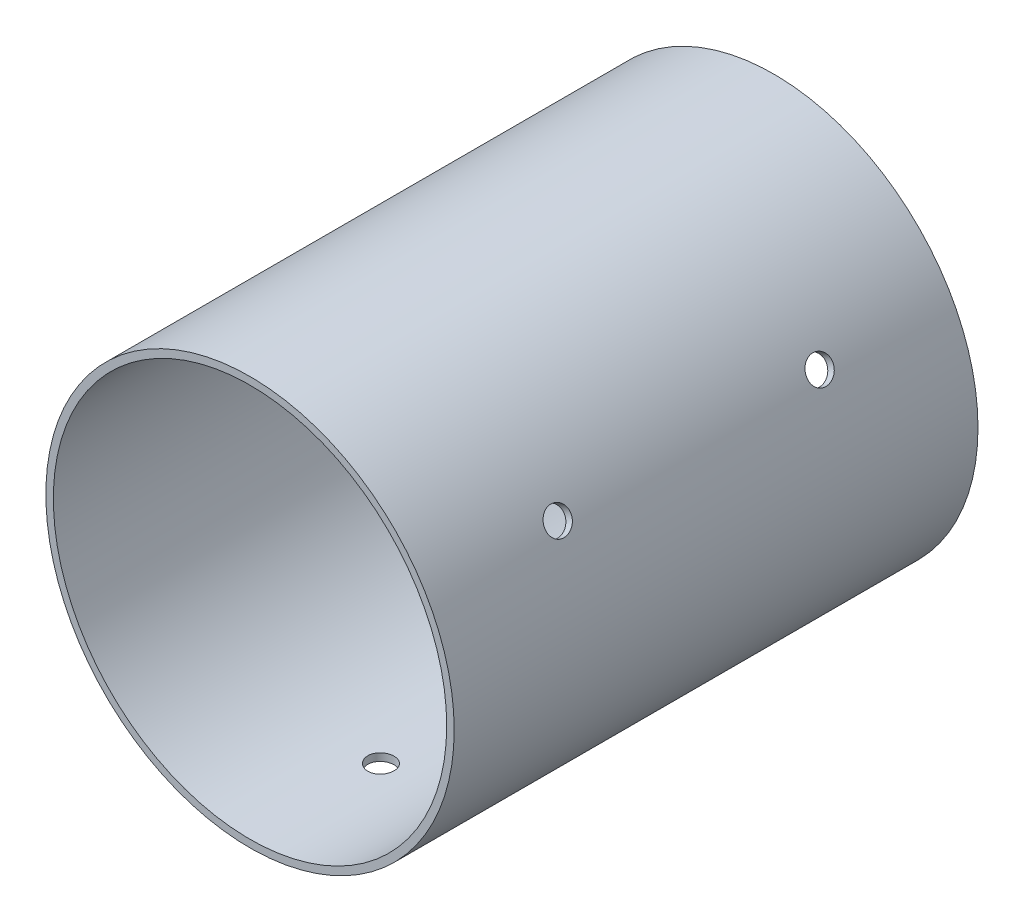
SolidWorks part; units mm, degrees
ref_plane "Front Plane" through (0, 0, 0) normal (0, 0, 1) x (1, 0, 0)
ref_plane "Top Plane" through (0, 0, 0) normal (0, 1, 0) x (1, 0, 0)
ref_plane "Right Plane" through (0, 0, 0) normal (1, 0, 0) x (0, 0, -1)
sketch "Sketch1" plane through (0, 0, 0) normal (0, 0, 1) x (1, 0, 0)
  circle A0 centre (0, 0) radius 49.5046
  circle A1 centre (0, 0) radius 47.6885
  dimension "D1" = 99.0092
  dimension "D2" = 95.377
extrude "Boss-Extrude1" add sketch "Sketch1" along normal blind 127
ref_axis "Axis1" through (0, 0, 127) along (0, 0, -1)
ref_plane "Plane1" through (0, 0, 0) normal (0.866, 0.5, 0) x (0, 0, -1)
sketch "Sketch4" plane through (0, 0, 0) normal (0, 1, 0) x (1, 0, 0)
  line L0 (0, -127) -> (0, 0) construction
  line L1 (-49.5046, -127) -> (49.5046, -127) construction
  line L2 (47.6885, 0) -> (-47.6885, 0) construction
  circle A0 centre (0, -31.75) radius 3.175
  circle A1 centre (0, -95.25) radius 3.175
  dimension "D1" = 6.35
  dimension "D2" = 31.75
  dimension "1.25" = 31.75
extrude "Cut-Extrude3" cut sketch "Sketch4" against normal through all
pattern_circular "CirPattern2" count 3 over 360 about axis through (0, 0, 127) along (0, 0, -1) of "Cut-Extrude3"
